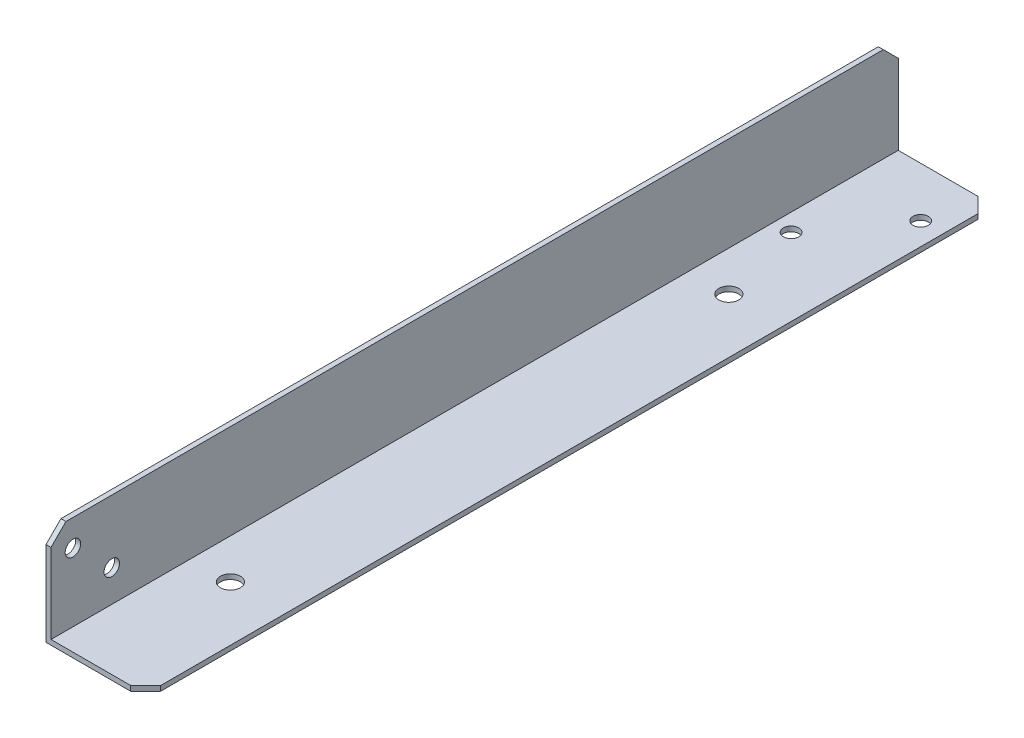
SolidWorks part; units mm, degrees
material "6063-T5"
ref_plane "Спереди" through (0, 0, 0) normal (0, 0, 1) x (1, 0, 0)
ref_plane "Сверху" through (0, 0, 0) normal (0, 1, 0) x (1, 0, 0)
ref_plane "Справа" through (0, 0, 0) normal (1, 0, 0) x (0, 0, -1)
sketch "Sketch1" plane through (0, 0, 0) normal (0, 0, 1) x (1, 0, 0)
  line L0 (0, 0) -> (20, 0)
  line L1 (20, 0) -> (20, 1)
  line L2 (20, 1) -> (1, 1)
  line L3 (1, 1) -> (1, 20)
  line L4 (1, 20) -> (0, 20)
  line L5 (0, 20) -> (0, 0)
  dimension "D1" = 20
  dimension "D2" = 20
  dimension "D3" = 1
  dimension "D4" = 1
extrude "Base" add sketch "Sketch1" along normal blind 170
chamfer "Chamfer1" distance 3 angle 45 4 edges at (20, 0.5, 170) (0.5, 20, 170) (0.5, 20, 0) (20, 0.5, 0)
sketch "Sketch4" plane through (2, 1, 0) normal (0, 1, 0) x (0, 0, -1)
  line L0 (-167, 2) -> (-3, 2) construction
  line L1 (0, -15) -> (0, 1) construction
  circle A0 centre (-10, -13.5) radius 1.55
  circle A1 centre (-25, -2.5) radius 1.55
  dimension "D5" = 3.1
  dimension "D6" = 3.1
  dimension "D1" = 4.5
  dimension "D2" = 15.5
  dimension "D3" = 10
  dimension "D4" = 25
extrude "CarriageSide" cut sketch "Sketch4" against normal through all
sketch "Sketch6" plane through (1, 0, 0) normal (1, 0, 0) x (0, 0, -1)
  line L1 (-170, 1) -> (-170, 17) construction
  line L2 (-170, 0) -> (0, 0) construction
  circle A0 centre (-165.6, 14.68) radius 1.55
  circle A1 centre (-157.8, 7.38) radius 1.55
  dimension "D5" = 3.1
  dimension "D1" = 7.8
  dimension "D2" = 7.38
  dimension "D3" = 7.3
  dimension "D4" = 4.4
extrude "CableChainSide" cut sketch "Sketch6" against normal up to surface (1 mm away) up to face at (0, 12.3333, 85)
sketch "Sketch7" plane through (0, 0, 0) normal (0, -1, 0) x (1, 0, 0)
  line L0 (0, 170) -> (0, 0) construction
  line L1 (0, 0) -> (17, 0) construction
  circle A0 centre (9, 142) radius 2
  circle A1 centre (9, 42) radius 2
  dimension "D1" = 4
  dimension "D2" = 9
  dimension "D3" = 142
  dimension "D4" = 42
extrude "Cut-Extrude1" cut sketch "Sketch7" against normal through all
equation "\"D2@Sketch1\"=\"D1@Sketch1\""
equation "\"D4@Sketch1\"=\"D3@Sketch1\""
